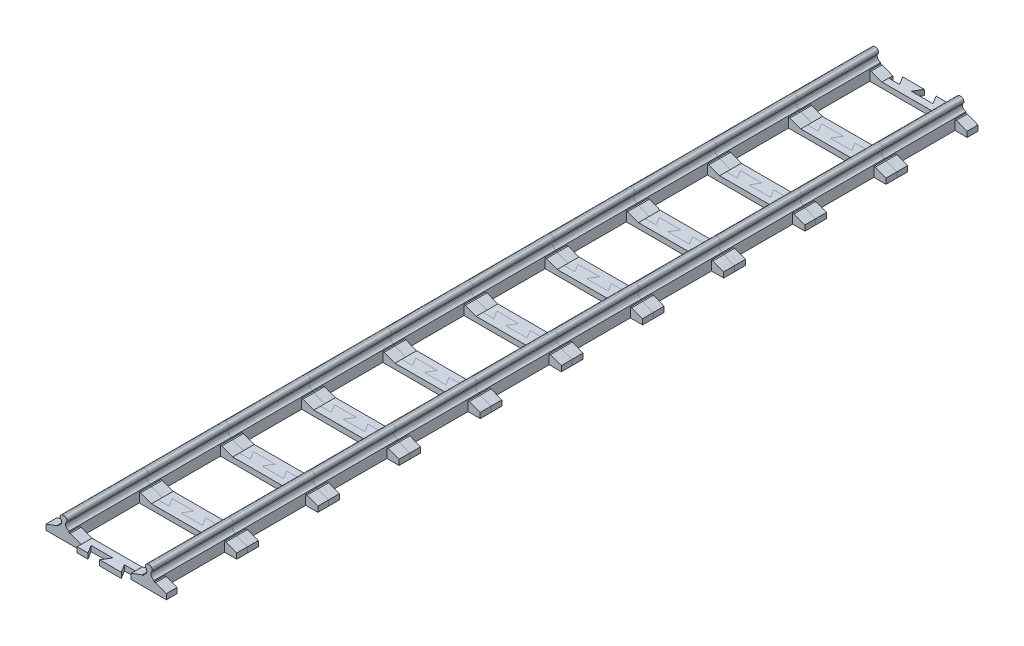
SolidWorks part; units mm, degrees
other "标注1"
sketch "草图3" plane through (-22.25, 4, -10) normal (-0.231, 0.6469, -0.7268) x (-0.9696, -0.2151, 0.1167)
other "标注2"
sketch "草图4" plane through (22.25, 8, -30) normal (0.0083, 0.0567, -0.9984) x (-0.9991, 0.0415, -0.0059)
ref_plane "前视基准面" through (0, 0, 0) normal (0, 0, 1) x (1, 0, 0)
ref_plane "上视基准面" through (0, 0, 0) normal (0, 1, 0) x (1, 0, 0)
ref_plane "右视基准面" through (0, 0, 0) normal (1, 0, 0) x (0, 0, -1)
other "Configuration Table"
sketch "草图1" plane through (0, 0, 0) normal (0, 1, 0) x (1, 0, 0)
  line L0 (-13.75, 9.5) -> (-13.75, -9.5)
  line L13 (-17.75, -9.5) -> (17.75, -9.5)
  line L21 (-17.75, -9.5) -> (-17.75, 9.5)
  line L22 (-17.75, 9.5) -> (17.75, 9.5)
  line L23 (17.75, -9.5) -> (17.75, 9.5)
  line L24 (-17.75, -9.5) -> (17.75, 9.5) construction
  line L25 (-17.75, 9.5) -> (17.75, -9.5) construction
  line L27 (13.75, 9.5) -> (13.75, -9.5)
  line L29 (-13.75, 0) -> (13.75, 0) construction
  line L32 (-22.25, 9.5) -> (22.25, 9.5)
  line L33 (-22.25, 9.5) -> (-22.25, 1.5)
  line L34 (-22.25, 1.5) -> (22.25, 1.5)
  line L35 (22.25, 9.5) -> (22.25, 1.5)
  point P0 (0, 0)
  point P15 (0, 1.5)
  dimension "D3" = 27.5
  dimension "D4" = 8
  dimension "D1" = 35.5
  dimension "D2" = 19
  dimension "D5" = 44.5
extrude "凸台-拉伸1" add sketch "草图1" along normal blind 4 contours L34 L21 L13 L0 | L34 L27 L13 L23 | L27 L34 L23 L22 | L21 L34 L0 L22 region at (-15.75, 0, -5.5) region at (-15.75, 0, 4) region at (15.75, 0, -5.5) region at (15.75, 0, 4)
extrude "凸台-拉伸2" add sketch "草图1<7>" along normal blind 3.5 contours L34 L35 L32 L33
sketch "草图1<7>" plane through (0, 0, 0) normal (0, 1, 0) x (1, 0, 0) same geometry as "草图1"
sketch "草图2" plane through (0, 0, -9.5) normal (0, 0, -1) x (-1, 0, 0)
  line L0 (18.25, 3.5) -> (22.25, 2)
  line L1 (22.25, 3.5) -> (18.25, 3.5)
  line L2 (22.25, 3.5) -> (22.25, 2)
  line L3 (22.25, 2) -> (18.25, 2) construction
  line L4 (18.25, 3.5) -> (18.25, 2) construction
  line L5 (-22.25, 2) -> (-18.25, 3.5)
  line L6 (-22.25, 3.5) -> (-18.25, 3.5)
  line L7 (-22.25, 3.5) -> (-22.25, 2)
  line L8 (-22.25, 2) -> (-18.25, 2) construction
  line L9 (-18.25, 3.5) -> (-18.25, 2) construction
  line L10 (13.75, 3.5) -> (-13.75, 3.5) construction
  line L11 (-13.25, 3.5) -> (-9.25, 3.5)
  line L12 (-13.25, 3.5) -> (-13.25, 2) construction
  line L13 (-13.25, 2) -> (-9.25, 2) construction
  line L14 (-9.25, 3.5) -> (-9.25, 2)
  line L15 (-13.75, 3.5) -> (-13.25, 3.5) construction
  line L16 (13.25, 3.5) -> (9.25, 3.5)
  line L17 (13.25, 3.5) -> (13.25, 2) construction
  line L18 (13.25, 2) -> (9.25, 2) construction
  line L19 (9.25, 3.5) -> (9.25, 2)
  line L20 (13.25, 3.5) -> (13.75, 3.5) construction
  line L21 (17.75, 3.5) -> (18.25, 3.5) construction
  line L22 (-13.25, 3.5) -> (-9.25, 2)
  line L23 (9.25, 2) -> (13.25, 3.5)
  line L24 (-9.25, 2) -> (9.25, 2)
  line L25 (-9.25, 3.5) -> (9.25, 3.5)
  line L26 (-15.75, 4) -> (-15.75, 6.5) construction
  line L27 (14.5, 8) -> (17, 8)
  line L28 (14.5, 8) -> (14.5, 6.5)
  line L29 (14.5, 6.5) -> (17, 6.5)
  line L30 (17, 8) -> (17, 6.5)
  line L31 (-17, 8) -> (-14.5, 8)
  line L32 (-17, 8) -> (-17, 6.5)
  line L33 (-17, 6.5) -> (-14.5, 6.5)
  line L34 (-14.5, 8) -> (-14.5, 6.5)
  line L35 (-13.75, 4) -> (-17.75, 4) construction
  line L36 (15.75, 6.5) -> (15.75, 4) construction
  line L37 (17.75, 4) -> (13.75, 4) construction
  line L38 (15, 6.5) -> (15, 4)
  line L39 (16.5, 6.5) -> (16.5, 4)
  line L40 (16.5, 4) -> (15.75, 4)
  line L41 (15.75, 4) -> (15, 4)
  line L42 (-16.5, 6.5) -> (-16.5, 4)
  line L43 (-16.5, 4) -> (-15.75, 4)
  line L44 (-15.75, 4) -> (-15, 4)
  line L45 (-15, 4) -> (-15, 6.5)
  line M9 (22.25, 3.5) -> (17.75, 3.5)
  line M11 (17.75, 4) -> (13.75, 4)
  line M13 (13.75, 3.5) -> (-13.75, 3.5)
  line M15 (-13.75, 4) -> (-17.75, 4)
  line M17 (-17.75, 3.5) -> (-22.25, 3.5)
  line M18 (-22.25, 3.5) -> (-22.25, 0)
  line M20 (22.25, 0) -> (22.25, 3.5)
  dimension "D1" = 4
  dimension "D2" = 1.5
  dimension "D3" = 2.5
  dimension "D4" = 1.5
  dimension "D5" = 2.5
  dimension "D6" = 1.5
extrude "切除-拉伸1" cut sketch "草图2" against normal through all contours L14 L24 L19 M13 | L19 L23 M13 | L22 L14 M13 | L5 M18 M17 | L0 M9 M20 region at (-20.9167, 3, -9.5) region at (20.9167, 3, -9.5) region at (10.5833, 3, -9.5) region at (0, 2.75, -9.5) region at (-10.5833, 3, -9.5)
extrude "凸台-拉伸4" add sketch "草图2<3>" against normal through all contours L34 L31 L32 L33 | L45 L33 L42 M15 | L30 L27 L28 L29 | L39 L29 L38 M11 region at (-15.75, 7.25, -9.5) region at (-15.75, 5.25, -9.5) region at (15.75, 7.25, -9.5) region at (15.75, 5.25, -9.5)
sketch "草图2<3>" plane through (0, 0, -9.5) normal (0, 0, -1) x (-1, 0, 0) same geometry as "草图2"
fillet "圆角1" radius 1 4 edges at (-16.5, 6.5, 0) (-15, 6.5, 0) (15, 6.5, 0) (16.5, 6.5, 0)
fillet "圆角2" radius 1.5 4 edges at (16.5, 4, 0) (15, 4, 0) (-15, 4, 0) (-16.5, 4, 0)
fillet "圆角3" radius 1 4 edges at (-17, 8, 0) (14.5, 8, 0) (17, 8, 0) (-14.5, 8, 0)
sketch "草图8" plane through (22.25, 0, 0) normal (1, 0, 0) x (0, 0, -1)
  line L0 (5.5, 0) -> (5.5, 18.5305)
  line L1 (9.5, 0) -> (1.5, 0) construction
mirror "镜向2" about plane through (0, 4, 9.5) normal (0, 0, -1) of bodies 192
sketch "草图9" plane through (0, 2, 0) normal (0, 1, 0) x (1, 0, 0)
  line L0 (-22.25, 5.5) -> (-9.25, 5.5)
  line L1 (-22.25, 1.5) -> (-22.25, 9.5) construction
  line L2 (-9.25, 1.5) -> (-9.25, 9.5) construction
  line L3 (-9.25, 5.5) -> (-9.25, 4)
  line L4 (-9.25, 4) -> (-5.25, 4)
  line L5 (-5.25, 4) -> (-7.0833, 7)
  line L6 (-7.0833, 7) -> (0.9167, 7)
  line L7 (0.9167, 7) -> (-0.9167, 4)
  line L8 (-0.9167, 4) -> (7.0833, 4)
  line L9 (7.0833, 4) -> (5.25, 7)
  line L10 (9.25, 1.5) -> (9.25, 9.5) construction
  line L11 (9.25, 5.5) -> (22.25, 5.5)
  line L12 (5.25, 7) -> (9.25, 7)
  line L13 (-22.25, 5.5) -> (-22.25, 9.5)
  line L14 (9.25, 7) -> (9.25, 5.5)
  line L15 (-22.25, 9.5) -> (22.25, 9.5)
  line L16 (22.25, 9.5) -> (22.25, 5.5)
  line L17 (22.25, 1.5) -> (22.25, 9.5) construction
  line L18 (-22.25, -24.5) -> (-9.25, -24.5)
  line L19 (-22.25, -20.5) -> (-22.25, -28.5) construction
  line L20 (-9.25, -20.5) -> (-9.25, -28.5) construction
  line L21 (-9.25, -24.5) -> (-9.25, -26)
  line L22 (-9.25, -26) -> (-5.25, -26)
  line L23 (-5.25, -26) -> (-7.0833, -23)
  line L24 (-7.0833, -23) -> (0.9167, -23)
  line L25 (0.9167, -23) -> (-0.9167, -26)
  line L26 (-0.9167, -26) -> (7.0833, -26)
  line L27 (7.0833, -26) -> (5.25, -23)
  line L28 (5.25, -23) -> (9.25, -23)
  line L29 (9.25, -20.5) -> (9.25, -28.5) construction
  line L30 (9.25, -23) -> (9.25, -24.5)
  line L31 (9.25, -24.5) -> (22.25, -24.5)
  line L32 (22.25, -20.5) -> (22.25, -28.5) construction
  line L33 (22.25, -24.5) -> (22.25, -28.5)
  line L34 (22.25, -28.5) -> (-22.25, -28.5)
  line L35 (-22.25, -28.5) -> (-22.25, -24.5)
  dimension "D1" = 3
  dimension "D2" = 8
  dimension "D3" = 4
extrude "切除-拉伸2" cut sketch "草图9" against normal through all both and the other way through all
pattern_linear "阵列(线性)1" count 10 spacing 30 along (0, 0, -1) of bodies 203
